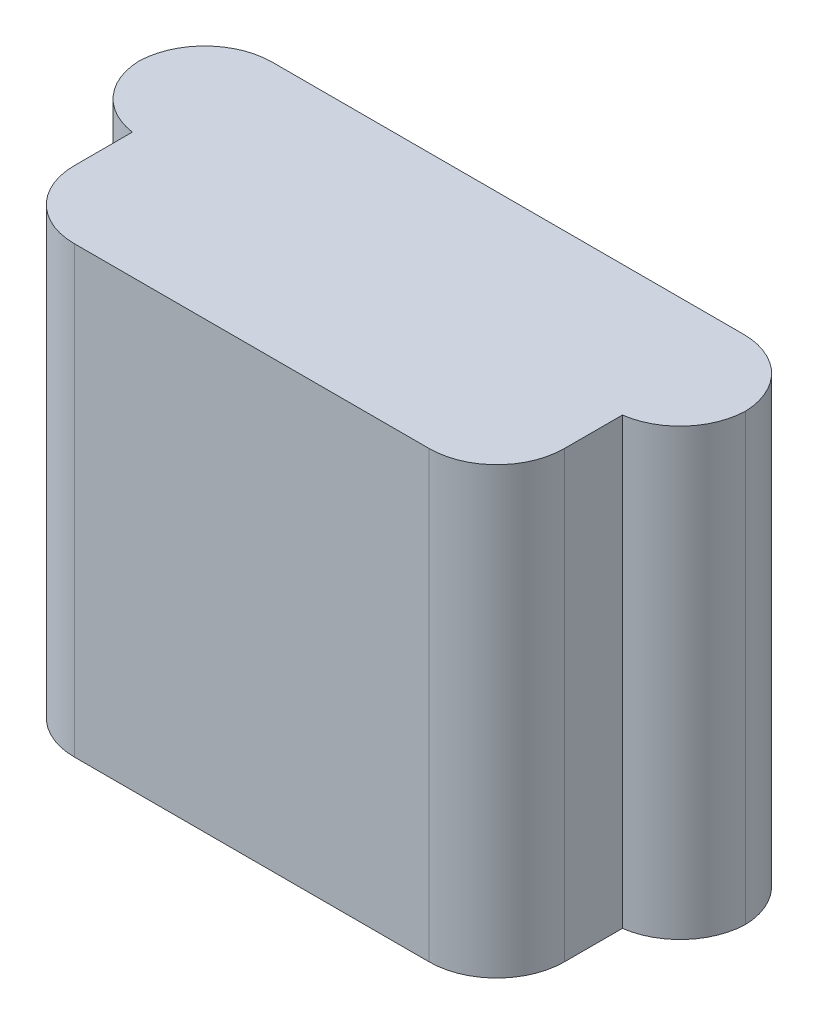
SolidWorks part; units mm, degrees
ref_plane "Front Plane" through (0, 0, 0) normal (0, 0, 1) x (1, 0, 0)
ref_plane "Top Plane" through (0, 0, 0) normal (0, 1, 0) x (1, 0, 0)
ref_plane "Right Plane" through (0, 0, 0) normal (1, 0, 0) x (0, 0, -1)
sketch "Sketch1" plane through (0, 0, 0) normal (0, 0, 1) x (1, 0, 0)
  line L0 (-45.6184, 0) -> (45.6184, 0)
  line L1 (45.6184, 0) -> (45.6184, 66.8782)
  line L2 (45.6184, 66.8782) -> (-45.6184, 66.8782)
  line L3 (-45.6184, 66.8782) -> (-45.6184, 0)
  point P4 (0, 0)
  dimension "D1" = 66.8782
  dimension "D2" = 91.2368
base flange "Base-Flange1" sketch "Sketch1" thickness 0.7366 reverse thickness direction no parameters "D1"=0.7366
sketch "Sketch6" plane through (0, 0, 0) normal (0, 0, 1) x (1, 0, 0)
  line L0 (-45.6184, 66.8782) -> (-45.6184, 0)
  line L1 (-45.6184, 66.8782) -> (-45.6184, 0) construction
  line L2 (-45.6184, 0) -> (45.6184, 0)
  line L3 (45.6184, 0) -> (45.6184, 66.8782)
  line L4 (45.6184, 66.8782) -> (-45.6184, 66.8782)
extrude "Boss-Extrude1" add sketch "Sketch6" along normal blind 37.7952
sketch "Sketch8" plane through (0, 0, 37.7952) normal (0, 0, 1) x (1, 0, 0)
  line L0 (-45.6184, 66.8782) -> (-36.8554, 66.8782)
  line L1 (45.6184, 66.8782) -> (-45.6184, 66.8782) construction
  line L2 (-36.8554, 66.8782) -> (-36.8554, 0)
  line L3 (-36.8554, 0) -> (-45.6184, 0)
  line L4 (-45.6184, 66.8782) -> (-45.6184, 0) construction
  line L5 (-45.6184, 0) -> (-45.6184, 66.8782)
  dimension "D1" = 8.763
extrude "Cut-Extrude2" cut sketch "Sketch8" against normal blind 18.8976 normal cut yes
mirror "Mirror1" about plane through (0, 0, 0) normal (1, 0, 0) of "Cut-Extrude2"
fillet "Fillet1" radius 10.16 6 edges at (-45.6184, 33.4391, 18.8976) (45.6184, 33.4391, 18.8976) (36.8554, 33.4391, 37.7952) (-36.8554, 33.4391, 37.7952) (45.6184, 33.4391, -0.7366) (-45.6184, 33.4391, -0.7366)
sketch "Bend-Lines1" [suppressed] plane through (0, 0, 0) normal (0, 1, 0) x (1, 0, 0)
sketch "Bounding-Box1" [suppressed] plane through (0, 0, 0) normal (0, 1, 0) x (1, 0, 0)
sheet metal parameters "Sheet-Metal1" thickness 0.7366 parameters "D1"=0.7366
flat pattern "Flat-Pattern1" [suppressed]
sketch "Bend-Lines2" plane through (0, 0, 0) normal (0, 1, 0) x (1, 0, 0)
sketch3d "Bounding-Box2" [suppressed]
  line L0 (45.6184, 0, 0) -> (-45.6184, 0, 0) construction
  line L1 (45.6184, 37.7952, 0) -> (-45.6184, 37.7952, 0) construction
  line L2 (45.6184, 0, 0) -> (45.6184, 37.7952, 0) construction
  line L3 (-45.6184, 0, 0) -> (-45.6184, 37.7952, 0) construction
sheet metal parameters "Sheet-Metal2" thickness 0.7366 parameters "D1"=0.7366
flat pattern "Flat-Pattern1"
sketch "Bend-Lines2" plane through (0, 0, 0) normal (0, 1, 0) x (1, 0, 0)
sketch3d "Bounding-Box2" [suppressed]
  line L0 (45.6184, 0, 0) -> (-45.6184, 0, 0) construction
  line L1 (45.6184, 66.8782, 0) -> (-45.6184, 66.8782, 0) construction
  line L2 (45.6184, 0, 0) -> (45.6184, 66.8782, 0) construction
  line L3 (-45.6184, 0, 0) -> (-45.6184, 66.8782, 0) construction
sheet metal parameters "Sheet-Metal4" thickness 0.7366 parameters "D1"=0.7366
flat pattern "Flat-Pattern1"
sketch "Bend-Lines2" plane through (0, 0, 0) normal (0, 1, 0) x (1, 0, 0)
sketch3d "Bounding-Box2" [suppressed]
  line L0 (45.6184, 0, 0) -> (-45.6184, 0, 0) construction
  line L1 (45.6184, 66.8782, 0) -> (-45.6184, 66.8782, 0) construction
  line L2 (45.6184, 0, 0) -> (45.6184, 66.8782, 0) construction
  line L3 (-45.6184, 0, 0) -> (-45.6184, 66.8782, 0) construction
sheet metal parameters "Sheet-Metal5" thickness 0.7366 parameters "D1"=0.7366
flat pattern "Flat-Pattern1"
sketch "Bend-Lines2" plane through (0, 0, 0) normal (0, 1, 0) x (1, 0, 0)
sketch3d "Bounding-Box2" [suppressed]
  line L0 (35.4584, 0, 0) -> (-35.4584, 0, 0) construction
  line L1 (35.4584, 66.8782, 0) -> (-35.4584, 66.8782, 0) construction
  line L2 (35.4584, 0, 0) -> (35.4584, 66.8782, 0) construction
  line L3 (-35.4584, 0, 0) -> (-35.4584, 66.8782, 0) construction
